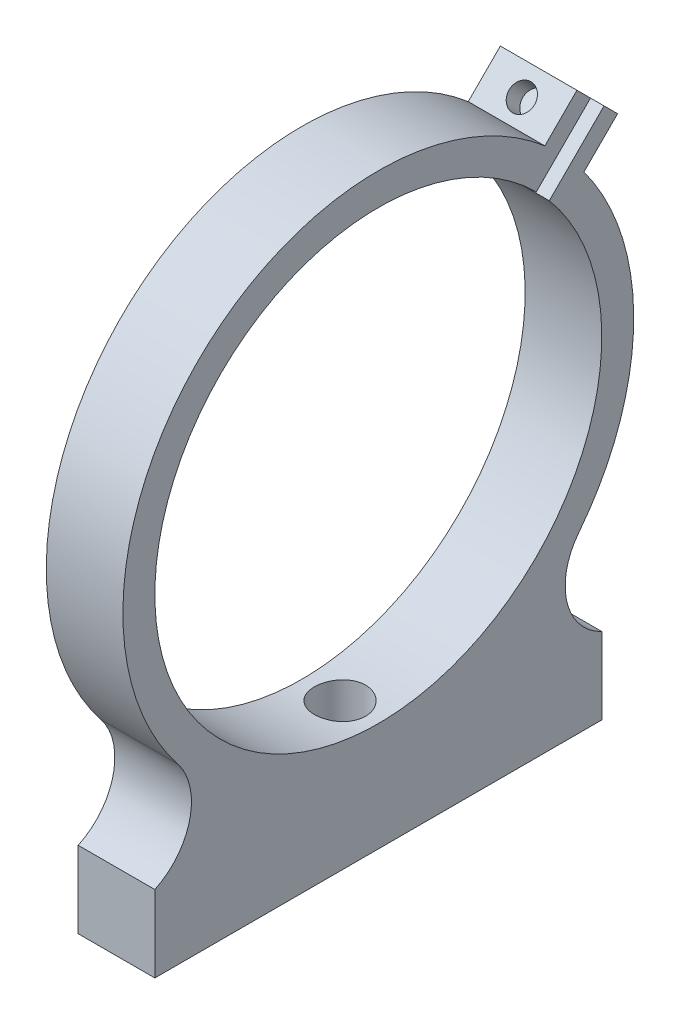
SolidWorks part; units mm, degrees
ref_plane "정면" through (0, 0, 0) normal (0, 0, 1) x (1, 0, 0)
ref_plane "윗면" through (0, 0, 0) normal (0, 1, 0) x (1, 0, 0)
ref_plane "우측면" through (0, 0, 0) normal (1, 0, 0) x (0, 0, -1)
sketch "스케치1" plane through (0, 0, 0) normal (1, 0, 0) x (0, 0, -1)
  line L0 (-35, -40) -> (35, -40)
  line L1 (35, -40) -> (35, -52)
  line L2 (35, -52) -> (-35, -52)
  line L3 (-35, -52) -> (-35, -40)
  line L4 (0, -52) -> (0, 40) construction
  circle A0 centre (0, 0) radius 35
  circle A1 centre (0, 0) radius 40
  arc A2 (-35, -40) -> (-18.1199, -35.6605) centre (-35, -5) ccw
  arc A3 (35, -40) -> (18.1199, -35.6605) centre (35, -5) cw
  point P8 (0, -40)
  dimension "D1" = 70
  dimension "D5" = 35
  dimension "D3" = 70
  dimension "D4" = 12
  dimension "D2" = 5
extrude "보스-돌출1" add sketch "스케치1" along normal blind 12 contours L3 L2 L1 L0 | A1 A0 | A2 L0 A1 | L4 L2 L1 L0 | L0 A3 A1 | L4 A1 A0 region at (0, -38.7122, 17.8025) region at (0, -46, 17.5) region at (0, -38.7122, -17.8025) region at (0, -46, -17.5) region at (0, -38.0302, 9.1078) region at (0, -37.5, -0.8944)
fillet "필렛1" radius 10 2 edges at (6, -35.6605, -18.1199) (6, -35.6605, 18.1199)
sketch "스케치2" plane through (0, -52, 0) normal (0, -1, 0) x (1, 0, 0)
  line L0 (6, 35) -> (6, -35) construction
  line L1 (12, 35) -> (0, 35) construction
  line L2 (12, -35) -> (0, -35) construction
  line L3 (0, 0) -> (12, 0) construction
  line L4 (12, -35) -> (12, 35) construction
  circle A0 centre (6, 0) radius 2
  circle A1 centre (6, 0) radius 4
  dimension "D1" = 4
  dimension "D2" = 8
extrude "컷-돌출1" cut sketch "스케치2" against normal blind 27 contours A0 region at (6, -52, 0)
extrude "컷-돌출2" cut sketch "스케치2<3>" against normal blind 18 from offset 6 offset against normal yes
sketch "스케치2<3>" plane through (0, -52, 0) normal (0, -1, 0) x (1, 0, 0) same geometry as "스케치2"
sketch "스케치3" plane through (12, 0, 0) normal (1, 0, 0) x (0, 0, -1)
  line L0 (0, 0) -> (33.234, 33.234)
  line L1 (0, 0) -> (2.1213, -2.1213)
  line L2 (33.234, 33.234) -> (35.3553, 31.1127)
  line L3 (2.1213, -2.1213) -> (35.3553, 31.1127)
  line L4 (0, 0) -> (40, 0) construction
  line L5 (1.0607, -1.0607) -> (34.2947, 32.1734) construction
  line L6 (33.234, 33.234) -> (31.1127, 35.3553)
  line L7 (35.3553, 31.1127) -> (37.4767, 28.9914)
  line L8 (31.1127, 35.3553) -> (26.0833, 30.3259)
  line L9 (37.4767, 28.9914) -> (32.2069, 23.7216)
  arc A0 (31.4123, -24.7642) -> (-31.4123, -24.7642) centre (0, 0) ccw construction
  point P16 (0, 0)
  point P17 (0, 0)
  point P18 (32.6984, 23.6671)
  point P19 (0, 0)
  point P20 (32.3958, 23.4629)
  point P21 (32.22, 23.7038)
  arc M9 (31.4123, -24.7642) -> (-31.4123, -24.7642) centre (0, 0) ccw
  circle M13 centre (0, 0) radius 35
  dimension "D1" = 45
  dimension "D2" = 3
  dimension "D3" = 47
  dimension "D4" = 3
extrude "보스-돌출2" add sketch "스케치3" against normal blind 12 contours L6 L8 L0 M9 | L9 L7 L3 M9 region at (12, 31.8093, -29.6823) region at (12, 27.4753, -33.8558)
extrude "컷-돌출3" cut sketch "스케치3<3>" against normal blind 12 contours L3 L0 M13 M9 region at (12, 25.4268, -27.5493)
sketch "스케치3<3>" plane through (12, 0, 0) normal (1, 0, 0) x (0, 0, -1) same geometry as "스케치3"
sketch "스케치4" plane through (0, -4.2426, -4.2426) normal (0, -0.7071, -0.7071) x (1, 0, 0)
  line L0 (12, -43.2737) -> (0, -43.2737) construction
  line L1 (12, -47) -> (12, -39.5474) construction
  line L2 (0, -47) -> (0, -39.5474) construction
  line L3 (6, -39.5474) -> (6, -47) construction
  line L4 (0, -39.5474) -> (12, -39.5474) construction
  line L5 (0, -47) -> (12, -47) construction
  circle A0 centre (6, -43.2737) radius 2
  dimension "D1" = 4
extrude "컷-돌출4" cut sketch "스케치4" against normal through all
